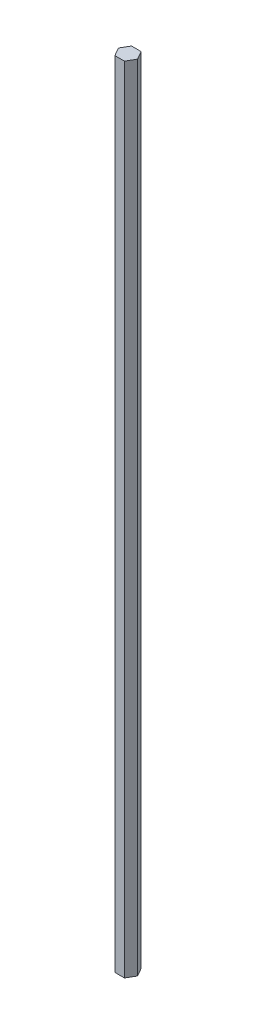
SolidWorks part; units mm, degrees
ref_plane "Front Plane" through (0, 0, 0) normal (0, 0, 1) x (1, 0, 0)
ref_plane "Top Plane" through (0, 0, 0) normal (0, 1, 0) x (1, 0, 0)
ref_plane "Right Plane" through (0, 0, 0) normal (1, 0, 0) x (0, 0, -1)
sketch "Sketch1" plane through (0, 0, 0) normal (0, 1, 0) x (1, 0, 0)
  line L7 (7.3323, 0) -> (3.6662, 6.35)
  line L8 (3.6662, 6.35) -> (-3.6662, 6.35)
  line L9 (-3.6662, 6.35) -> (-7.3323, 0)
  line L10 (-7.3323, 0) -> (-3.6662, -6.35)
  line L11 (-3.6662, -6.35) -> (3.6662, -6.35)
  line L12 (3.6662, -6.35) -> (7.3323, 0)
  circle A0 centre (0, 0) radius 6.35 construction
  dimension "D1" = 12.7
extrude "Boss-Extrude1" add sketch "Sketch1" along normal mid plane 606.552
sketch "Sketch3" plane through (0, 0, 0) normal (1, 0, 0) x (0, 0, -1)
  line L0 (0, 8.0656) -> (0, -8.0656) construction
  line L1 (0, 327.3297) -> (0, -319.0358) construction
